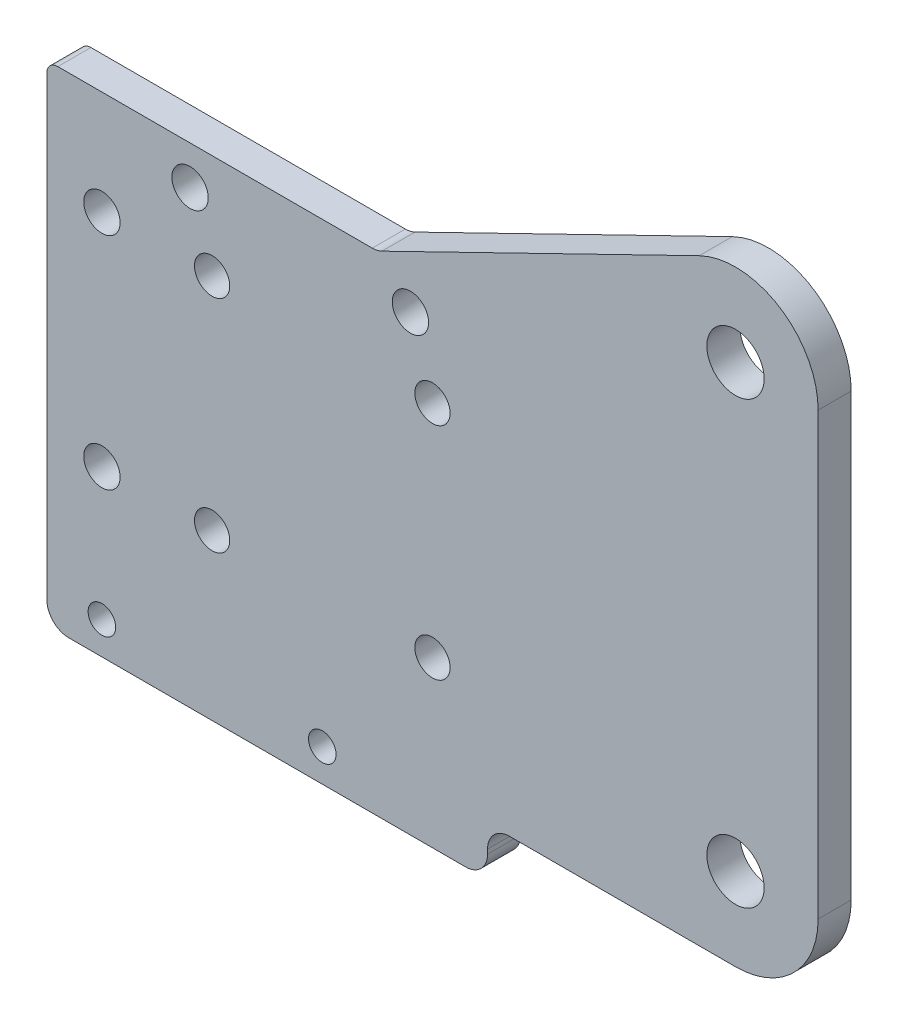
SolidWorks part; units mm, degrees
ref_plane "前视基准面" through (0, 0, 0) normal (0, 0, 1) x (1, 0, 0)
ref_plane "上视基准面" through (0, 0, 0) normal (0, 1, 0) x (1, 0, 0)
ref_plane "右视基准面" through (0, 0, 0) normal (1, 0, 0) x (0, 0, -1)
sketch "草图1" plane through (0, 0, 0) normal (0, 0, 1) x (1, 0, 0)
  line L0 (0, 0) -> (50000, 0) construction
  line L1 (-35, -27.5) -> (27.5, -27.5)
  line L2 (-35, -27.5) -> (-35, 27.5)
  line L3 (-35, 27.5) -> (27.5, 27.5)
  line L4 (35, -20) -> (35, 20)
  line L5 (-35, -27.5) -> (35, 27.5) construction
  line L6 (-35, 27.5) -> (35, -27.5) construction
  circle A0 centre (27.5, 20) radius 2.6
  circle A1 centre (27.5, -20) radius 2.6
  arc A4 (27.5, -27.5) -> (35, -20) centre (27.5, -20) ccw
  arc A5 (27.5, 27.5) -> (35, 20) centre (27.5, 20) cw
  point P0 (0, 0)
  dimension "D1" = 5.2
  dimension "D5" = 7.5
  dimension "D2" = 70
  dimension "60" = 55
  dimension "D3" = 40
  dimension "D4" = 7.5
extrude "凸台-拉伸1" add sketch "草图1" along normal blind 3
sketch "草图2" plane through (0, 0, 3) normal (0, 0, 1) x (1, 0, 0)
  line L0 (-35, 12.5) -> (-5, 12.5)
  line L1 (-35, 27.5) -> (-35, -27.5) construction
  line L2 (-5, 12.5) -> (24.2135, 26.7416)
  line L3 (-35, -27.5) -> (27.5, -27.5) construction
  line L4 (-35, 12.5) -> (-35, 37.5)
  line L5 (-35, 37.5) -> (27.5, 37.5)
  line L6 (27.5, 37.5) -> (27.5, 27.5)
  circle A0 centre (27.5, 20) radius 7.5 construction
  arc A1 (24.2135, 26.7416) -> (27.5, 27.5) centre (27.5, 20) cw
  dimension "D1" = 15
  dimension "D4" = 10
  dimension "D2" = 40
  dimension "D3" = 30
extrude "切除-拉伸1" cut sketch "草图2" against normal blind 3
sketch "草图3" plane through (0, 0, 3) normal (0, 0, 1) x (1, 0, 0)
  line L0 (-35, 12.5) -> (-35, -27.5) construction
  line L1 (-20, -16.95) -> (0, -16.95) construction
  line L2 (-20, -16.95) -> (-20, 3.05) construction
  line L3 (-20, 3.05) -> (0, 3.05) construction
  line L4 (0, -16.95) -> (0, 3.05) construction
  line L5 (-20, -16.95) -> (0, 3.05) construction
  line L6 (-20, 3.05) -> (0, -16.95) construction
  line L7 (-20, -6.95) -> (0, -6.95) construction
  line L9 (-10, 3.05) -> (-10, -16.95) construction
  line L10 (-35, 12.5) -> (-5, 12.5) construction
  circle A0 centre (-20, 3.05) radius 1.6
  circle A2 centre (0, 3.05) radius 1.6
  circle A3 centre (0, -16.95) radius 1.6
  circle A4 centre (-20, -16.95) radius 1.6
  circle A5 centre (27.5, 20) radius 15 construction
  circle A6 centre (27.5, -20) radius 15 construction
  point P0 (-10, -6.95)
  dimension "D4" = 3.2
  dimension "D5" = 9.45
  dimension "D6" = 30
  dimension "D7" = 30
  dimension "D1" = 20
  dimension "D2" = 20
  dimension "D3" = 15
extrude "切除-拉伸2" cut sketch "草图3" against normal blind 3
fillet "圆角1" radius 1 2 edges at (-35, -27.5, 1.5) (-35, 12.5, 1.5)
sketch "草图4" plane through (0, 0, 3) normal (0, 0, 1) x (1, 0, 0)
  line L0 (-20, 3.05) -> (0, -16.95) construction
  line L1 (0, 3.05) -> (-20, -16.95) construction
  line L3 (-15, -14.45) -> (-5, -14.45) construction
  line L4 (-15, -14.45) -> (-15, 0.55) construction
  line L5 (-15, 0.55) -> (-5, 0.55) construction
  line L6 (-5, -14.45) -> (-5, 0.55) construction
  line L7 (-15, -14.45) -> (-5, 0.55) construction
  line L8 (-15, 0.55) -> (-5, -14.45) construction
  circle A0 centre (-5, 0.55) radius 1.75
  circle A1 centre (-15, 0.55) radius 1.75
  circle A2 centre (-15, -14.45) radius 1.75
  circle A3 centre (-5, -14.45) radius 1.75
  point P8 (-10, -6.95)
  dimension "D3" = 3.5
  dimension "D4" = 3.5
  dimension "D5" = 3.5
  dimension "D6" = 3.5
  dimension "D1" = 15
  dimension "D2" = 10
extrude "切除-拉伸3" [suppressed] cut sketch "草图4" against normal blind 10
sketch "草图5" plane through (0, 0, 0) normal (0, 0, -1) x (-1, 0, 0)
  line L0 (34, -27.5) -> (-27.5, -27.5) construction
  line L1 (35, -26.5) -> (-5, -26.5)
  line L2 (35, -26.5) -> (35, -31.9)
  line L3 (35, -31.9) -> (-5, -31.9)
  line L4 (-5, -26.5) -> (-5, -31.9)
  dimension "D1" = 40
  dimension "D2" = 4.4
extrude "凸台-拉伸2" add sketch "草图5" against normal up to surface (3 mm away) up to face at (-21.6, -16.95, 3)
sketch "草图6" plane through (0, 0, 0) normal (0, 0, -1) x (-1, 0, 0)
  line L0 (-5, -31.9) -> (35, -31.9) construction
  line L1 (35, 11.5) -> (35, -31.9) construction
  circle A0 centre (30, -28.95) radius 1.25
  circle A1 centre (10, -28.95) radius 1.25
  dimension "D1" = 2.95
  dimension "D2" = 5
  dimension "D4" = 2.5
  dimension "D3" = 2
extrude "切除-拉伸4" cut sketch "草图6" against normal blind 4
fillet "圆角2" radius 2 4 edges at (-35, -31.9, 1.5) (-5, 12.5, 1.5) (5, -27.5, 1.5) (5, -31.9, 1.5)
sketch "草图7" plane through (0, 0, 3) normal (0, 0, 1) x (1, 0, 0)
  line L0 (-20, -16.95) -> (-20, 3.05)
  line L1 (-20, -6.95) -> (-48.6106, -6.95) construction
  line L2 (-35, 11.5) -> (-35, -29.9) construction
  line L3 (-34, 12.5) -> (-5.4615, 12.5) construction
  circle A0 centre (-30, 3.05) radius 1.65
  circle A1 centre (-30, -16.95) radius 1.65
  circle A2 centre (-22, 9) radius 1.65
  circle A3 centre (-2, 9.2) radius 1.65
  dimension "D1" = 3.3
  dimension "D2" = 10
  dimension "D3" = 5
  dimension "D4" = 3.3
  dimension "D5" = 3.3
  dimension "D6" = 3.5
  dimension "D7" = 3.3
  dimension "D8" = 20
  dimension "D9" = 13
extrude "切除-拉伸5" cut sketch "草图7" against normal blind 10 contours A2 | A3 | A0 | A1 region at (-30, 3.05, 3) region at (-30, -16.95, 3) region at (-22, 9, 3) region at (-2, 9.2, 3)
